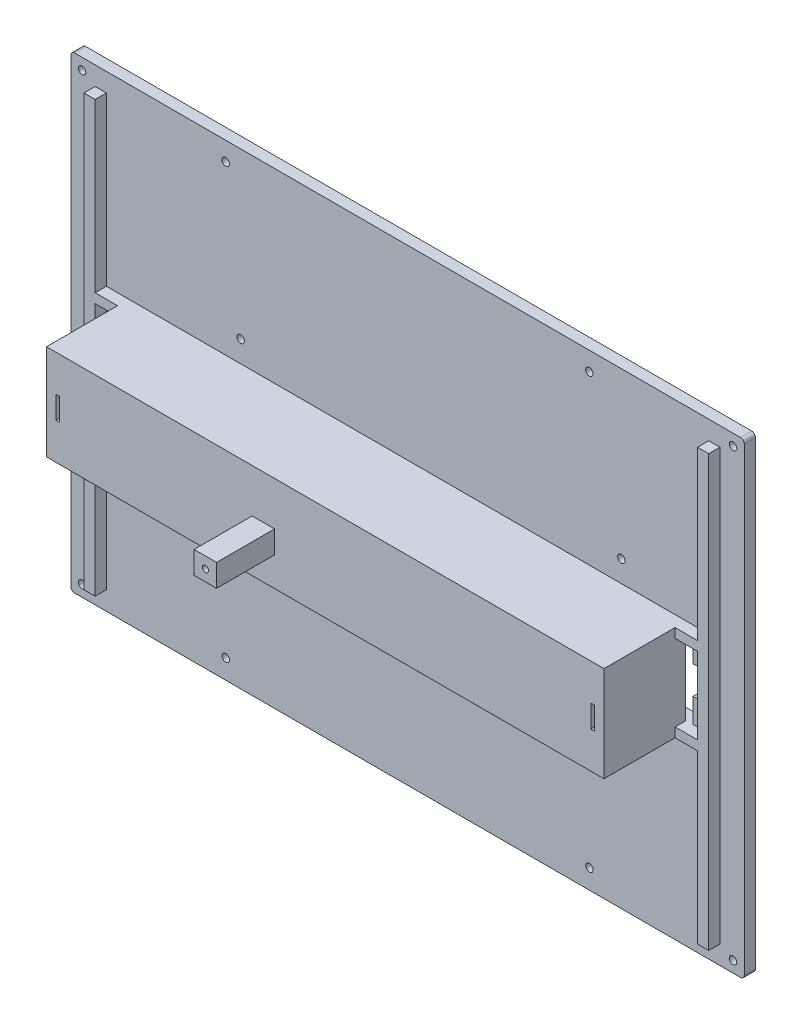
SolidWorks part; units mm, degrees
ref_plane "前视基准面" through (0, 0, 0) normal (0, 0, 1) x (1, 0, 0)
ref_plane "上视基准面" through (0, 0, 0) normal (0, 1, 0) x (1, 0, 0)
ref_plane "右视基准面" through (0, 0, 0) normal (1, 0, 0) x (0, 0, -1)
sketch "草图1" plane through (0, 0, 0) normal (0, 0, 1) x (1, 0, 0)
  line L1 (-90, 62.5) -> (90, 62.5)
  line L2 (-90, 62.5) -> (-90, -62.5)
  line L3 (-90, -62.5) -> (90, -62.5)
  line L4 (90, 62.5) -> (90, -62.5)
  line L5 (-90, 62.5) -> (90, -62.5) construction
  line L6 (-90, -62.5) -> (90, 62.5) construction
  point P0 (0, 0)
  dimension "D1" = 125
  dimension "D2" = 180
extrude "凸台-拉伸1" add sketch "草图1" along normal blind 3
sketch "草图7" plane through (0, 0, 0) normal (0, 0, -1) x (-1, 0, 0)
  line L1 (-72, 10.25) -> (72, 10.25)
  line L2 (-72, 10.25) -> (-72, -10.25)
  line L3 (-72, -10.25) -> (72, -10.25)
  line L4 (72, 10.25) -> (72, -10.25)
  line L5 (0, 0) -> (72.729, 0) construction
  line L8 (0, 0) -> (0, -50.9103) construction
  dimension "D1" = 20.5
  dimension "D2" = 144
extrude "电池位切除-拉伸3" cut sketch "草图7" against normal up to next
sketch "草图8" plane through (0, 0, 3) normal (0, 0, 1) x (1, 0, 0)
  line L12 (72, 10.25) -> (72, -10.25) construction
  line L13 (-74.5, 12.75) -> (74.5, 12.75)
  line L14 (-74.5, 12.75) -> (-74.5, -12.75)
  line L15 (-74.5, -12.75) -> (74.5, -12.75)
  line L16 (74.5, 12.75) -> (74.5, -12.75)
  line L17 (-72, -10.25) -> (-72, 10.25) construction
  line L18 (-72, 10.25) -> (72, 10.25) construction
  line L19 (72, -10.25) -> (-72, -10.25) construction
  line L20 (-72, 10.25) -> (72, 10.25)
  line L21 (72, -10.25) -> (-72, -10.25)
  line L22 (72, 10.25) -> (72, -10.25)
  line L23 (-72, -10.25) -> (-72, 10.25) construction
  line L24 (-72, -10.25) -> (-72, 10.25)
  dimension "D1" = 2.5
  dimension "D2" = 2.5
  dimension "D3" = 2.5
  dimension "D4" = 2.5
extrude "凸台-拉伸2" add sketch "草图8" along normal blind 22
sketch "草图9" plane through (0, 0, 25) normal (0, 0, 1) x (1, 0, 0)
  line L0 (74.5, 12.75) -> (-74.5, 12.75) construction
  line L5 (74.5, 12.75) -> (-74.5, 12.75)
  line L6 (-74.5, -12.75) -> (74.5, -12.75) construction
  line L7 (-74.5, -12.75) -> (74.5, -12.75)
  line L8 (74.5, -12.75) -> (74.5, 12.75) construction
  line L9 (74.5, -12.75) -> (74.5, 12.75)
  line L10 (-74.5, 12.75) -> (-74.5, -12.75) construction
  line L11 (-74.5, 12.75) -> (-74.5, -12.75)
extrude "凸台-拉伸3" add sketch "草图9" against normal blind 2.5
sketch "草图4" plane through (0, 0, 0) normal (0, 0, -1) x (-1, 0, 0)
  line L0 (72, -10.25) -> (72, 10.25) construction
  line L5 (72, 0) -> (84.6307, 0) construction
  line L10 (83.2374, -53.4277) -> (79.3374, -53.4277) construction
  line L11 (83.2374, -49.6277) -> (83.2374, -53.4277) construction
  line L12 (79.3374, -49.6277) -> (83.2374, -49.6277) construction
  line L29 (72, -4) -> (74.5, -4)
  line L30 (74.5, -4) -> (74.5, 4)
  line L31 (74.5, 4) -> (72, 4)
  line L32 (72, 4) -> (72, -4)
  dimension "D1" = 8
  dimension "D2" = 2.5
extrude "切除-拉伸2" cut sketch "草图4" against normal blind 2 from offset 1.5 offset against normal yes
sketch "草图10" plane through (0, 0, 25) normal (0, 0, 1) x (1, 0, 0)
  line L0 (-16.5366, -1.9347) -> (8.5541, -1.9347) construction
  line L2 (-19.5366, 1.0653) -> (-19.5366, -4.9347)
  line L4 (-13.5366, 1.0653) -> (-13.5366, -4.9347)
  line L5 (-16.5366, -1.9347) -> (-16.5366, 4.0653) construction
  line L6 (0, 0) -> (60.8594, 0) construction
  line L7 (0, 0) -> (0, 60.5) construction
  line L8 (75, 60.5) -> (-75, 60.5) construction
  line L9 (-19.5366, 1.0653) -> (-13.5366, 1.0653)
  line L10 (-19.5366, -4.9347) -> (-13.5366, -4.9347)
  circle A0 centre (-16.5366, -1.9347) radius 0.825
  dimension "D2" = 1.65
  dimension "D1" = 6
extrude "凸台-拉伸4" add sketch "草图10" along normal up to surface (15.5 mm away)
sketch "草图11" plane through (0, 0, 0) normal (0, 0, -1) x (-1, 0, 0)
  circle A0 centre (-48.6147, -57.3) radius 1 construction
  circle A1 centre (-44.6, -18.3) radius 1 construction
  circle A2 centre (57.15, -18.3) radius 1 construction
  circle A3 centre (48.5747, -57.3) radius 1 construction
  circle A4 centre (87, 59.5) radius 1
  circle A5 centre (48.6147, 57.5) radius 1 construction
  circle A6 centre (-57.15, 18.5) radius 1 construction
  circle A7 centre (-48.5747, 57.5) radius 1 construction
  circle A8 centre (-48.6147, -57.3) radius 1
  circle A9 centre (-44.6, -18.3) radius 1
  circle A10 centre (57.15, -18.3) radius 1
  circle A11 centre (48.5747, -57.3) radius 1
  circle A13 centre (48.6147, 57.5) radius 1
  circle A14 centre (-57.15, 18.5) radius 1
  circle A15 centre (-48.5747, 57.5) radius 1
  circle A16 centre (44.6, 18.5) radius 1 construction
  circle A17 centre (44.6, 18.5) radius 1
  circle A18 centre (87, -59.5) radius 1
  circle A19 centre (-87, -59.5) radius 1
  circle A20 centre (-87, 59.5) radius 1
  dimension "D1" = 2
  dimension "D2" = 2
  dimension "D3" = 2
  dimension "D4" = 2
extrude "固定螺丝切除-拉伸3" cut sketch "草图11" against normal up to next
sketch "草图12" plane through (0, 0, 0) normal (0, 0, -1) x (-1, 0, 0)
  circle A0 centre (-48.5747, 57.5) radius 2
  circle A1 centre (-57.15, 18.5) radius 2
  circle A2 centre (-44.6, -18.3) radius 2
  circle A3 centre (-48.6147, -57.3) radius 2
  circle A4 centre (48.5747, -57.3) radius 2
  circle A5 centre (57.15, -18.3) radius 2
  circle A7 centre (-87, 59.5) radius 2
  circle A8 centre (48.6147, 57.5) radius 2
  circle A9 centre (44.6, 18.5) radius 2
  circle A10 centre (-87, -59.5) radius 2
  circle A11 centre (87, -59.5) radius 2
  circle A12 centre (87, 59.5) radius 2
  dimension "D1" = 4
  dimension "D2" = 4
  dimension "D3" = 4
  dimension "D4" = 4
  dimension "D5" = 4
extrude "固定螺丝凹陷切除-拉伸4" cut sketch "草图12" against normal blind 1.2
fillet "圆角1" radius 1 4 edges at (90, -62.5, 1.5) (-90, -62.5, 1.5) (-90, 62.5, 1.5) (90, 62.5, 1.5)
sketch "草图13" plane through (0, 0, 25) normal (0, 0, 1) x (1, 0, 0)
  line L0 (72, 10.25) -> (72, -10.25) construction
  line L1 (72, 3) -> (71, 3)
  line L2 (72, 3) -> (72, -3)
  line L3 (72, -3) -> (71, -3)
  line L4 (71, 3) -> (71, -3)
  line L5 (-72, -10.25) -> (-72, 10.25) construction
  line L6 (-71, 3) -> (-72, 3)
  line L7 (-71, 3) -> (-71, -3)
  line L8 (-71, -3) -> (-72, -3)
  line L9 (-72, 3) -> (-72, -3)
  line L10 (72, 0) -> (59.7453, 0) construction
  dimension "D1" = 1
  dimension "D2" = 6
  dimension "D3" = 1
  dimension "D4" = 6
extrude "切除-拉伸3" cut sketch "草图13" against normal up to next
sketch "草图14" plane through (0, 0, 22.5) normal (0, 0, -1) x (-1, 0, 0)
  line L0 (72, 10.25) -> (-72, 10.25) construction
  line L1 (-71, 10.25) -> (-69, 10.25)
  line L2 (-71, 10.25) -> (-71, 5.25)
  line L3 (-71, 5.25) -> (-69, 5.25)
  line L4 (-69, 10.25) -> (-69, 5.25)
  line L5 (-72, 0) -> (-60.8543, 0) construction
  line L6 (-72, 10.25) -> (-72, -10.25) construction
  line L7 (72, 0) -> (63.4917, 0) construction
  line L8 (69, 10.25) -> (71, 10.25)
  line L9 (69, 10.25) -> (69, 5.75)
  line L10 (69, 5.75) -> (71, 5.75)
  line L11 (71, 10.25) -> (71, 5.75)
  line L12 (72, -10.25) -> (72, 10.25) construction
  line L13 (71, -10.25) -> (71, -5.75)
  line L14 (69, -5.75) -> (71, -5.75)
  line L15 (69, -10.25) -> (69, -5.75)
  line L16 (69, -10.25) -> (71, -10.25)
  line L17 (-69, -10.25) -> (-69, -5.25)
  line L18 (-71, -5.25) -> (-69, -5.25)
  line L19 (-71, -10.25) -> (-71, -5.25)
  line L20 (-71, -10.25) -> (-69, -10.25)
  dimension "D1" = 1
  dimension "D2" = 2
  dimension "D3" = 4.5
  dimension "D4" = 1
  dimension "D5" = 2
  dimension "D6" = 5
extrude "凸台-拉伸5" add sketch "草图14" along normal blind 16
sketch "草图15" plane through (0, 0, 0) normal (0, 0, -1) x (-1, 0, 0)
  line L7 (-72, -10.25) -> (72, -10.25) construction
  line L8 (-76.3, 10.25) -> (-72, 10.25)
  line L9 (-76.3, 10.25) -> (-76.3, 3.75)
  line L10 (-76.3, -10.25) -> (-72, -10.25)
  line L11 (-72, 10.25) -> (-72, -10.25)
  line L12 (-76.3, 3.75) -> (-79.3365, 3.75)
  line L14 (-76.3, -3.75) -> (-79.3365, -3.75)
  line L15 (-79.3365, 3.75) -> (-79.3365, -3.75)
  line L16 (72, 10.25) -> (-72, 10.25) construction
  line L17 (-76.3, -3.75) -> (-76.3, -10.25)
  line L18 (-76.1, -10.05) -> (-76.1, 10.05) construction
  line L19 (-79.2365, 3.5) -> (-79.2365, -3.5) construction
  dimension "D1" = 6.5
  dimension "D2" = 6.5
  dimension "D3" = 0.2
  dimension "D4" = 0.1
extrude "切除-拉伸6" cut sketch "草图15" against normal blind 3.2
sketch "草图17" plane through (0, 0, 0) normal (0, 0, -1) x (-1, 0, 0)
  line L0 (-76.3, 3.75) -> (-79.3365, 3.75) construction
  line L1 (-81.8365, 3.75) -> (-79.3365, 3.75)
  line L2 (-81.8365, 3.75) -> (-81.8365, -3.75)
  line L3 (-81.8365, -3.75) -> (-79.3365, -3.75)
  line L4 (-79.3365, 3.75) -> (-79.3365, -3.75)
  dimension "D1" = 2.5
extrude "切除-拉伸7" cut sketch "草图17" against normal blind 1.5
fillet "圆角2" radius 0.25 26 edges at (-71, 10.25, 14.5) (-69, 10.25, 14.5) (-69, -10.25, 14.5) (-71, -10.25, 14.5) (71, -10.25, 14.5) (69, -10.25, 14.5) (69, 10.25, 14.5) (71, 10.25, 14.5) (-70, 10.25, 6.5) (-71, 8, 6.5) (-70, 5.75, 6.5) (-69, 8, 6.5) (-69, -8, 6.5) (-70, -5.75, 6.5) (-71, -8, 6.5) (-70, -10.25, 6.5) (71, -7.75, 6.5) (70, -5.25, 6.5) (69, -7.75, 6.5) (70, -10.25, 6.5) (70, 10.25, 6.5) (69, 7.75, 6.5) (70, 5.25, 6.5) (71, 7.75, 6.5) (79.3365, 0, 3) (81.8365, 0, 0)
sketch "草图18" plane through (0, 0, 3) normal (0, 0, 1) x (1, 0, 0)
  line L0 (0, 0) -> (0, 49.5083) construction
  line L1 (-83.5, 57.5) -> (-80.5, 57.5)
  line L2 (-83.5, 57.5) -> (-83.5, -57.5)
  line L3 (-83.5, -57.5) -> (-80.5, -57.5)
  line L4 (-80.5, 57.5) -> (-80.5, 12.75)
  line L5 (89, 62.5) -> (-89, 62.5) construction
  line L6 (-89, -62.5) -> (89, -62.5) construction
  line L7 (-74.5, 12.75) -> (-74.5, -12.75) construction
  line L12 (-80.5, 10.25) -> (-80.5, -10.25)
  line L13 (-74.5, 12.75) -> (-80.5, 12.75)
  line L14 (-74.5, 12.75) -> (-74.5, 10.25)
  line L15 (-74.5, 10.25) -> (-80.5, 10.25)
  line L17 (-74.5, -12.75) -> (-80.5, -12.75)
  line L18 (-74.5, -12.75) -> (-74.5, -10.25)
  line L19 (-74.5, -10.25) -> (-80.5, -10.25)
  line L21 (-80.5, -12.75) -> (-80.5, -57.5)
  line L22 (80.5, -12.75) -> (80.5, -57.5)
  line L23 (74.5, -10.25) -> (80.5, -10.25)
  line L24 (74.5, -12.75) -> (74.5, -10.25)
  line L25 (74.5, -12.75) -> (80.5, -12.75)
  line L26 (74.5, 10.25) -> (80.5, 10.25)
  line L27 (74.5, 12.75) -> (74.5, 10.25)
  line L28 (74.5, 12.75) -> (80.5, 12.75)
  line L29 (80.5, 10.25) -> (80.5, -10.25)
  line L30 (80.5, 57.5) -> (80.5, 12.75)
  line L31 (83.5, -57.5) -> (80.5, -57.5)
  line L32 (83.5, 57.5) -> (83.5, -57.5)
  line L33 (83.5, 57.5) -> (80.5, 57.5)
  dimension "D1" = 5
  dimension "D2" = 5
  dimension "D3" = 3
  dimension "D4" = 6
  dimension "D5" = 2.5
extrude "凸台-拉伸6" add sketch "草图18" along normal blind 3
